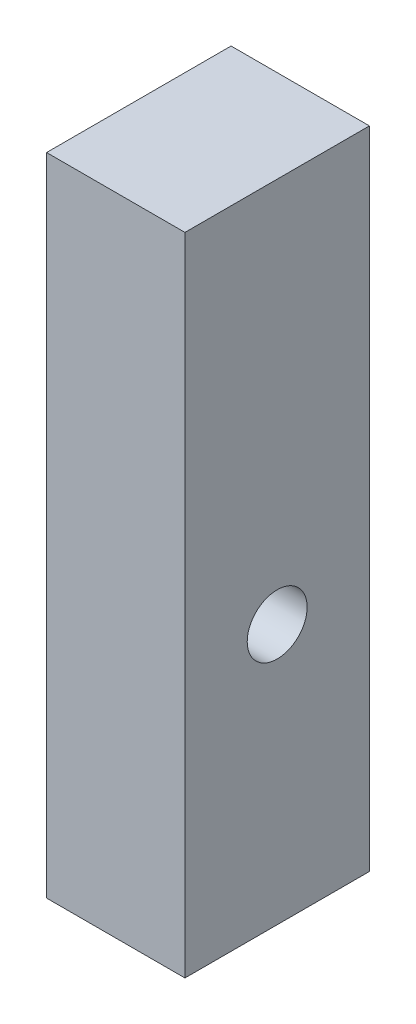
SolidWorks part; units mm, degrees
ref_plane "Front Plane" through (0, 0, 0) normal (0, 0, 1) x (1, 0, 0)
ref_plane "Top Plane" through (0, 0, 0) normal (0, 1, 0) x (1, 0, 0)
ref_plane "Right Plane" through (0, 0, 0) normal (1, 0, 0) x (0, 0, -1)
sketch "Sketch18" plane through (0, 0, 0) normal (0, -1, 0) x (-1, 0, 0)
  line L1 (-7.5, 10) -> (7.5, 10)
  line L2 (-7.5, 10) -> (-7.5, -10)
  line L3 (-7.5, -10) -> (7.5, -10)
  line L4 (7.5, 10) -> (7.5, -10)
  point P5 (-7.5, 0)
  point P6 (0, 10)
  dimension "D1" = 20
  dimension "D2" = 15
extrude "PinionHolder" add sketch "Sketch18" along normal blind 70
sketch "Sketch19" plane through (-7.5, 0, 0) normal (-1, 0, 0) x (0, 0, 1)
  line L0 (8.25, 0) -> (-8.25, 0) construction
  circle A0 centre (0, -41.8) radius 3.25
  dimension "D2" = 6.5
  dimension "D1" = 41.8
extrude "PinionHole" cut sketch "Sketch19" against normal through all
ref_plane "Plane1" through (0, 0, 0) normal (-1, 0, 0) x (0, 0, 1)
sketch "Sketch22" plane through (0, 0, 0) normal (-1, 0, 0) x (0, 0, 1)
  circle A0 centre (0, -41.8) radius 7.975
  dimension "D1" = 15.95
extrude "BearingHole" cut sketch "Sketch22" against normal mid plane 5 contours A0
